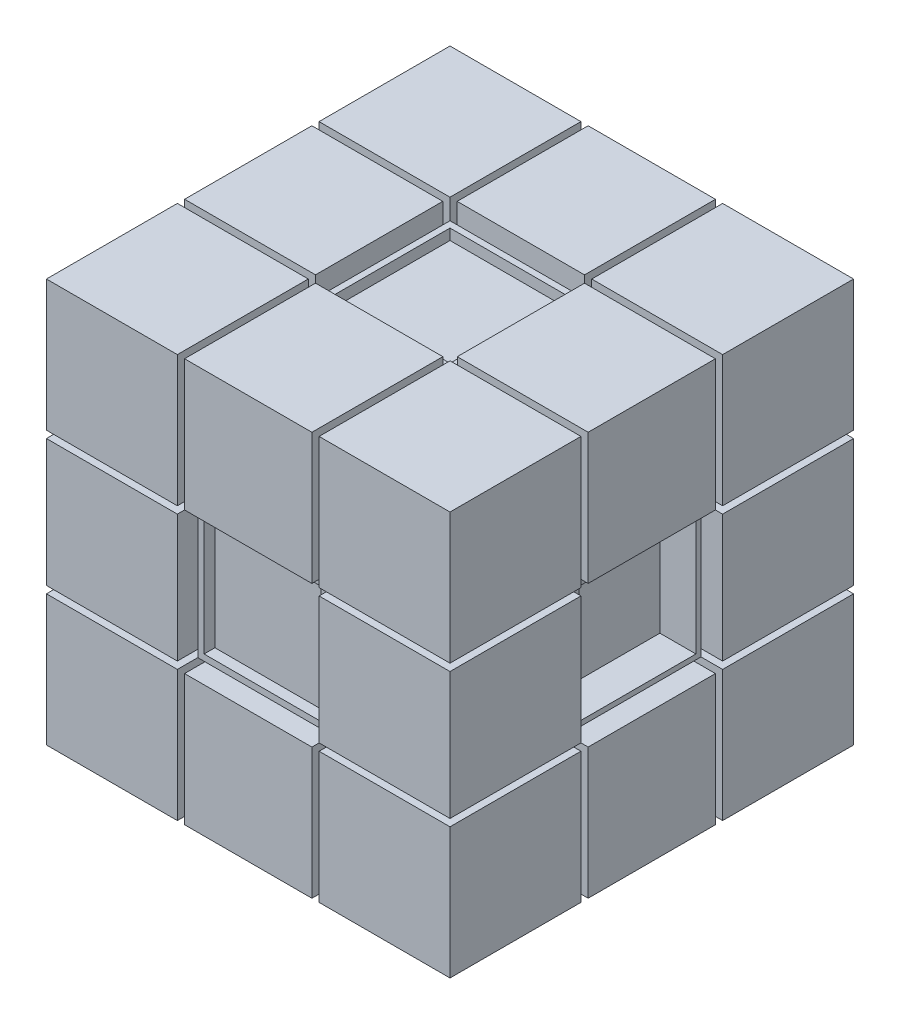
SolidWorks part; units mm, degrees
note: The reader was unsure of these and kept them because the rebuilt part matched: shared geometry of "Sketch2<3>", "Sketch12<3>", "Sketch14<2>".
ref_plane "Płaszczyzna przednia" through (0, 0, 0) normal (0, 0, 1) x (1, 0, 0)
ref_plane "Płaszczyzna górna" through (0, 0, 0) normal (0, 1, 0) x (1, 0, 0)
ref_plane "Płaszczyzna prawa" through (0, 0, 0) normal (1, 0, 0) x (0, 0, -1)
sketch "Sketch1" plane through (0, 0, 0) normal (0, 1, 0) x (1, 0, 0)
  line L1 (28, -28) -> (-28, -28)
  line L2 (28, -28) -> (28, 28)
  line L3 (28, 28) -> (-28, 28)
  line L4 (-28, -28) -> (-28, 28)
  line L5 (28, -28) -> (-28, 28) construction
  line L6 (28, 28) -> (-28, -28) construction
  point P0 (0, 0)
  dimension "D1" = 56
extrude "Boss-Extrude1" add sketch "Sketch1" along normal mid plane 56
sketch "Sketch2" plane through (0, 28, 0) normal (0, 1, 0) x (1, 0, 0)
  line L1 (8.125, -8.125) -> (-8.125, -8.125)
  line L2 (8.125, -8.125) -> (8.125, 8.125)
  line L3 (8.125, 8.125) -> (-8.125, 8.125)
  line L4 (-8.125, -8.125) -> (-8.125, 8.125)
  line L5 (8.125, -8.125) -> (-8.125, 8.125) construction
  line L6 (8.125, 8.125) -> (-8.125, -8.125) construction
  line L7 (9, -9) -> (-9, -9)
  line L8 (9, -9) -> (9, 9)
  line L9 (9, 9) -> (-9, 9)
  line L10 (-9, -9) -> (-9, 9)
  line L11 (9, -9) -> (-9, 9) construction
  line L12 (9, 9) -> (-9, -9) construction
  point P0 (0, 0)
  point P6 (0, 0)
  dimension "D1" = 16.25
  dimension "D2" = 18
extrude "Cut-Extrude1" cut sketch "Sketch2" against normal mid plane 7 contours L4 L1 L2 L3
extrude "Cut-Extrude6" cut sketch "Sketch2<3>" against normal blind 2
sketch "Sketch2<3>" plane through (0, 28, 0) normal (0, 1, 0) x (1, 0, 0) same geometry as "Sketch2"
sketch "Sketch3" plane through (0, 0, 0) normal (0, 0, 1) x (1, 0, 0)
  line L0 (-28, 0) -> (28, 0) construction
  line L1 (-28, 28) -> (-28, -28) construction
  line L2 (28, 28) -> (28, -28) construction
sketch "Sketch6" plane through (0, 28, 0) normal (0, 1, 0) x (1, 0, 0)
  line L0 (-9.3333, 9.3333) -> (-9.3333, 9.33)
  line L1 (28, 28) -> (-28, 28) construction
  line L2 (-28, -28) -> (28, -28) construction
  line L3 (-28, 28) -> (-28, -28) construction
  line L4 (9.3367, 9.3367) -> (9.3367, 9.33)
  line L5 (-9.3333, 9.33) -> (-9.33, 9.33)
  line L7 (-9.3333, -9.33) -> (-9.33, -9.33)
  line L8 (-9.8333, 28) -> (-9.8333, 9.83)
  line L9 (-28, 8.83) -> (-9.8333, 8.83)
  line L10 (8.8367, 28) -> (8.8367, 9.83)
  line L11 (-28, -9.83) -> (-9.83, -9.83)
  line L12 (-8.8333, 28) -> (-8.8333, 9.83)
  line L13 (-28, 9.83) -> (-9.83, 9.83)
  line L14 (9.8367, 28) -> (9.8367, 9.83)
  line L15 (-28, -8.83) -> (-9.8333, -8.83)
  line L16 (-28, 9.83) -> (-28, 8.83)
  line L17 (-9.8333, 8.83) -> (-9.8333, -8.83)
  line L18 (28, -28) -> (-28, -28)
  line L19 (28, -28) -> (28, 28)
  line L20 (28, 28) -> (-28, 28)
  line L21 (-28, -28) -> (-28, 28)
  line L22 (28, -28) -> (9.83, -9.83) construction
  line L23 (28, 28) -> (9.33, 9.33) construction
  line L24 (-9.8333, 28) -> (-9.8333, -28) construction
  line L25 (-9.3333, 28) -> (-9.3333, -28) construction
  line L26 (-8.8333, 9.83) -> (8.8367, 9.83)
  line L27 (-28, 9.83) -> (28, 9.83) construction
  line L28 (-8.8333, 8.8333) -> (-8.8333, -8.8333)
  line L29 (-8.8333, 28) -> (-8.8333, -28) construction
  line L30 (9.33, 9.33) -> (9.3367, 9.33)
  line L31 (-28, 9.33) -> (28, 9.33) construction
  line L32 (-9.83, 9.83) -> (-28, 28) construction
  line L33 (-9.33, 9.33) -> (-9.3333, 9.3333) construction
  line L34 (-9.3333, -9.33) -> (-9.3333, -9.3333)
  line L35 (-8.8333, 8.83) -> (8.8367, 8.83)
  line L36 (-28, 8.83) -> (28, 8.83) construction
  line L37 (8.8367, 8.8367) -> (8.8367, -8.8367)
  line L38 (8.8367, 28) -> (8.8367, -28) construction
  line L39 (9.83, 9.83) -> (28, 9.83)
  line L40 (9.3367, 28) -> (9.3367, -28) construction
  line L41 (8.8367, 8.8367) -> (-8.8333, -8.8333) construction
  line L42 (9.8367, 8.83) -> (28, 8.83)
  line L43 (9.3367, -9.33) -> (9.3367, -9.3367)
  line L44 (9.33, -9.33) -> (9.3367, -9.33)
  line L45 (9.8367, 8.83) -> (9.8367, -8.83)
  line L46 (9.8367, 28) -> (9.8367, -28) construction
  line L47 (-28, -9.33) -> (28, -9.33) construction
  line L48 (8.8367, -9.83) -> (8.8367, -28)
  line L49 (9.83, -9.83) -> (28, -9.83)
  line L50 (-28, -9.83) -> (28, -9.83) construction
  line L51 (9.3367, -9.3367) -> (9.33, -9.33) construction
  line L52 (9.8367, -9.83) -> (9.8367, -28)
  line L53 (9.8367, -8.83) -> (28, -8.83)
  line L54 (-28, -8.83) -> (28, -8.83) construction
  line L55 (8.8367, -8.8367) -> (-8.8333, 8.8333) construction
  line L56 (-9.8333, -9.83) -> (-9.8333, -28)
  line L57 (-8.8333, -8.83) -> (8.8367, -8.83)
  line L58 (-9.83, -9.83) -> (-28, -28) construction
  line L59 (-8.8333, -9.83) -> (8.8367, -9.83)
  line L60 (-8.8333, -9.83) -> (-8.8333, -28)
  line L61 (-9.33, -9.33) -> (-9.3333, -9.3333) construction
  point P32 (0, 0)
  dimension "D1" = 18.6667
  dimension "D2" = 18.67
  dimension "D3" = 18.67
  dimension "D4" = 18.67
  dimension "D5" = 0.5
  dimension "D6" = 0.5
extrude "Cut-Extrude2" cut sketch "Sketch6" against normal blind 18.67
sketch "Sketch11" plane through (0, 0, 0) normal (0, 1, 0) x (1, 0, 0)
  line L0 (0.0017, 28) -> (0.0017, -28) construction
  line L1 (8.8367, 28) -> (-8.8333, 28) construction
  line L2 (-8.8333, -28) -> (8.8367, -28) construction
pattern_circular "CirPattern6" count 4 over 360 about axis through (0, 0, 0) along (1, 0, 0) of "Cut-Extrude6", "Cut-Extrude1", "Cut-Extrude2"
sketch "Sketch12" plane through (-28, 0, 0) normal (-1, 0, 0) x (0, 0, 1)
  line L1 (8.125, -8.125) -> (-8.125, -8.125)
  line L2 (8.125, -8.125) -> (8.125, 8.125)
  line L3 (8.125, 8.125) -> (-8.125, 8.125)
  line L4 (-8.125, -8.125) -> (-8.125, 8.125)
  line L5 (8.125, -8.125) -> (-8.125, 8.125) construction
  line L6 (8.125, 8.125) -> (-8.125, -8.125) construction
  line L8 (9, -9) -> (-9, -9)
  line L9 (9, -9) -> (9, 9)
  line L10 (9, 9) -> (-9, 9)
  line L11 (-9, -9) -> (-9, 9)
  line L12 (9, -9) -> (-9, 9) construction
  line L13 (9, 9) -> (-9, -9) construction
  point P0 (0, 0)
  point P5 (0, 0)
  dimension "D1" = 16.25
  dimension "D2" = 18
extrude "Cut-Extrude7" cut sketch "Sketch12" against normal blind 2
extrude "Cut-Extrude8" cut sketch "Sketch12<3>" against normal blind 7 contours L4 L1 L2 L3
sketch "Sketch12<3>" plane through (-28, 0, 0) normal (-1, 0, 0) x (0, 0, 1) same geometry as "Sketch12"
sketch "Sketch13" plane through (-28, 0, 0) normal (-1, 0, 0) x (0, 0, 1)
  line L0 (8.83, 8.83) -> (-8.83, 8.83)
  line L1 (9.83, -9.83) -> (-9.83, -9.83)
  line L2 (9.83, -9.83) -> (9.83, 9.83)
  line L3 (9.83, 9.83) -> (-9.83, 9.83)
  line L4 (-9.83, -9.83) -> (-9.83, 9.83)
  line L5 (9.83, -9.83) -> (-9.83, 9.83) construction
  line L6 (9.83, 9.83) -> (-9.83, -9.83) construction
  line L7 (-8.83, -8.83) -> (-8.83, 8.83)
  line L8 (8.83, -8.83) -> (-8.83, -8.83)
  line L9 (8.83, -8.83) -> (8.83, 8.83)
  point P0 (0, 0)
  dimension "D1" = 1
extrude "Cut-Extrude9" cut sketch "Sketch13" against normal blind 18.67
sketch "Sketch14" plane through (28, 0, 0) normal (1, 0, 0) x (0, 0, -1)
  line L1 (8.125, -8.125) -> (-8.125, -8.125)
  line L2 (8.125, -8.125) -> (8.125, 8.125)
  line L3 (8.125, 8.125) -> (-8.125, 8.125)
  line L4 (-8.125, -8.125) -> (-8.125, 8.125)
  line L5 (8.125, -8.125) -> (-8.125, 8.125) construction
  line L6 (8.125, 8.125) -> (-8.125, -8.125) construction
  line L7 (9, -9) -> (-9, -9)
  line L8 (9, -9) -> (9, 9)
  line L9 (9, 9) -> (-9, 9)
  line L10 (-9, -9) -> (-9, 9)
  line L11 (9, -9) -> (-9, 9) construction
  line L12 (9, 9) -> (-9, -9) construction
  point P0 (0, 0)
  point P6 (0, 0)
  dimension "D1" = 16.25
  dimension "D2" = 18
extrude "Cut-Extrude10" cut sketch "Sketch14" against normal blind 2
extrude "Cut-Extrude11" cut sketch "Sketch14<2>" against normal blind 7 contours L4 L1 L2 L3
sketch "Sketch14<2>" plane through (28, 0, 0) normal (1, 0, 0) x (0, 0, -1) same geometry as "Sketch14"
sketch "Sketch15" plane through (28, 0, 0) normal (1, 0, 0) x (0, 0, -1)
  line L1 (9.83, -9.83) -> (-9.83, -9.83)
  line L2 (9.83, -9.83) -> (9.83, 9.83)
  line L3 (9.83, 9.83) -> (-9.83, 9.83)
  line L4 (-9.83, -9.83) -> (-9.83, 9.83)
  line L5 (9.83, -9.83) -> (-9.83, 9.83) construction
  line L6 (9.83, 9.83) -> (-9.83, -9.83) construction
  line L7 (-8.83, -8.83) -> (-8.83, 8.83)
  line L8 (8.83, 8.83) -> (-8.83, 8.83)
  line L9 (8.83, -8.83) -> (8.83, 8.83)
  line L10 (8.83, -8.83) -> (-8.83, -8.83)
  dimension "D1" = 1
extrude "Cut-Extrude12" cut sketch "Sketch15" against normal blind 18.67
